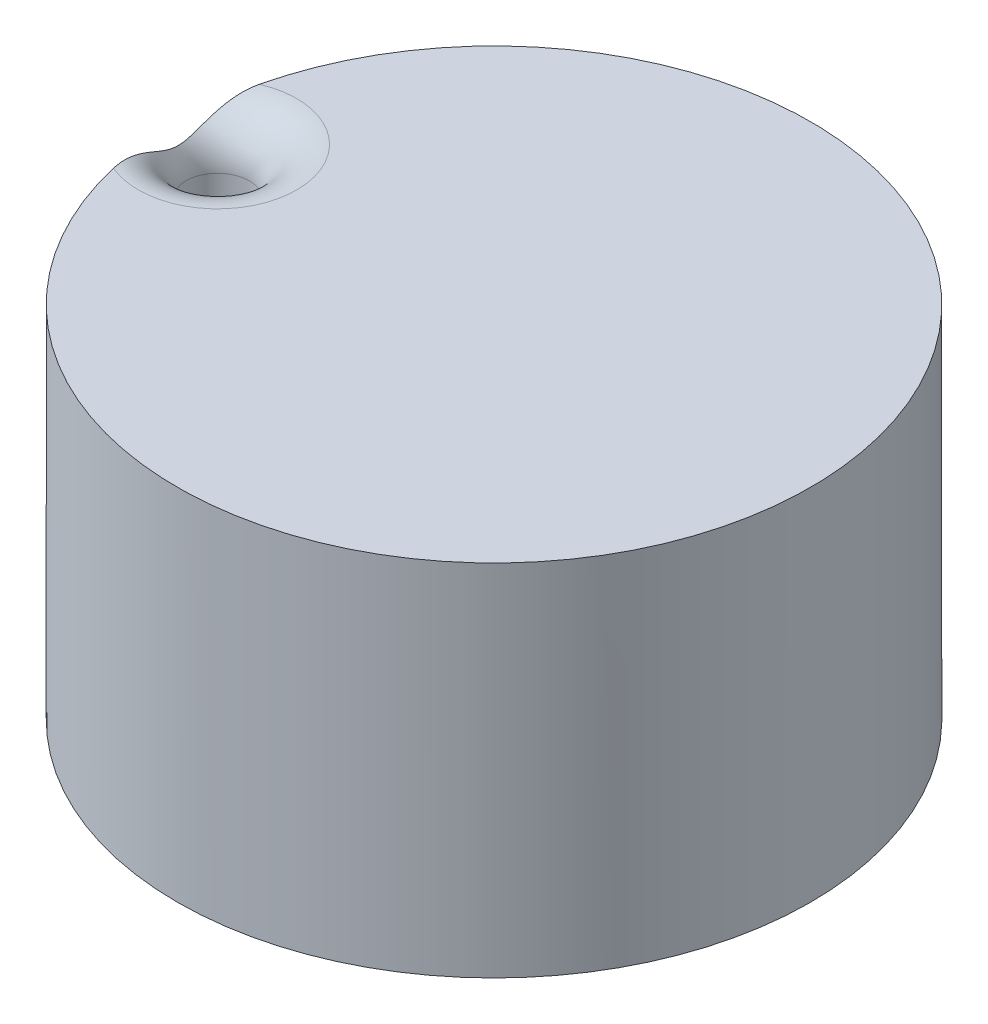
SolidWorks part; units mm, degrees
ref_plane "Front Plane" through (0, 0, 0) normal (0, 0, 1) x (1, 0, 0)
ref_plane "Top Plane" through (0, 0, 0) normal (0, 1, 0) x (1, 0, 0)
ref_plane "Right Plane" through (0, 0, 0) normal (1, 0, 0) x (0, 0, -1)
sketch "Sketch2" plane through (0, 0, 0) normal (0, 1, 0) x (1, 0, 0)
  circle A0 centre (0, 0) radius 50.8
extrude "Boss-Extrude1" add sketch "Sketch2" along normal blind 57.658
sketch "Sketch3" plane through (0, 57.658, 0) normal (0, 1, 0) x (1, 0, 0)
  circle A1 centre (-44.4329, 0.0886) radius 5.08
extrude "Cut-Extrude1" cut sketch "Sketch3" against normal blind 57.658 contours A1
fillet "Fillet1" radius 7.62 1 edges at (-44.4329, 57.658, 4.9914)
sketch "Sketch4" plane through (0, 57.658, 0) normal (0, 1, 0) x (1, 0, 0)
  circle A1 centre (-26.162, 0) radius 3.175
  circle A2 centre (26.162, 0) radius 3.175
  circle A3 centre (0, 26.162) radius 3.175
  circle A4 centre (0, -26.162) radius 3.175
